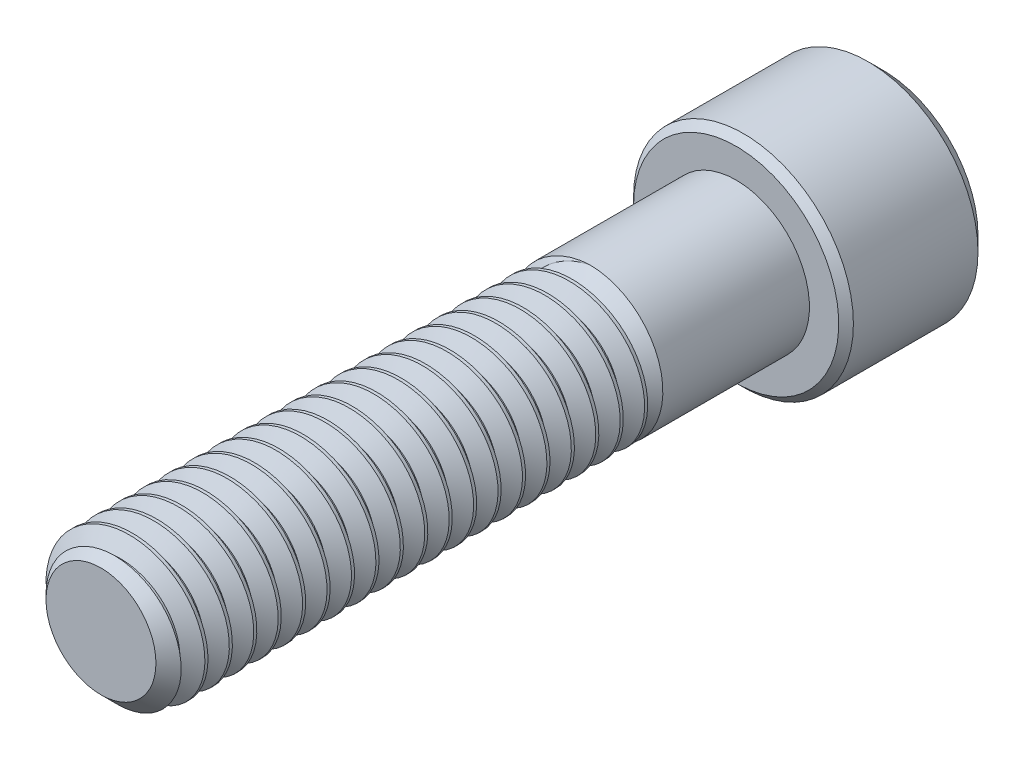
SolidWorks part; units mm, degrees
ref_plane "Front Plane" through (0, 0, 0) normal (0, 0, 1) x (1, 0, 0)
ref_plane "Top Plane" through (0, 0, 0) normal (0, 1, 0) x (1, 0, 0)
ref_plane "Right Plane" through (0, 0, 0) normal (1, 0, 0) x (0, 0, -1)
sketch "Sketch1" plane through (0, 0, 0) normal (0, 0, 1) x (1, 0, 0)
  line L0 (0, 4.7625) -> (0, -4.7625) construction
  circle A0 centre (0, 0) radius 4.7625
  dimension "OD" = 9.525
extrude "Extrude1" add sketch "Sketch1" against normal blind 41.275
sketch "Sketch2" plane through (0, 0, 0) normal (0, 0, 1) x (1, 0, 0)
  circle A0 centre (0, 0) radius 4.7625 construction
  circle A1 centre (0, 0) radius 4.7625
curve "Helix/Spiral1" pitch 1.5875 height 34.925 turns 22 parameters "pitch"=1.5875
chamfer "Chamfer3" distance 1.1906 angle 45 1 edges at (4.7625, 0, 0)
sketch "Sketch3" plane through (0, 0, 0) normal (1, 0, 0) x (0, 0, -1)
  line L0 (-1.3891, 4.7625) -> (-0.7938, 3.7314)
  line L1 (-0.7938, 3.7314) -> (-0.5953, 3.7314)
  line L2 (-0.5953, 3.7314) -> (0, 4.7625)
  line L3 (-1.3891, 4.7625) -> (0, 4.7625)
  line L4 (-0.6945, 4.7625) -> (-0.6945, 3.7314) construction
  line L5 (-1.0914, 4.2469) -> (-0.2977, 4.2469) construction
  line L6 (0, 4.7625) -> (0, -4.7625) construction
  dimension "D1" = 0.1984
  dimension "D2" = 0.7937
  dimension "D3" = 60
sweep "Cut-Sweep1" cut profiles "Sketch3" path "Helix/Spiral1"
sketch "Sketch5" plane through (0, 0, 0) normal (1, 0, 0) x (0, 0, -1)
  line L1 (41.275, 4.7625) -> (31.75, 4.7625)
  line L2 (41.275, 4.7625) -> (41.275, 0)
  line L3 (41.275, 0) -> (31.75, 0)
  line L4 (31.75, 4.7625) -> (31.75, 0) construction
  line L6 (0, 0) -> (9.9695, 0) construction
  line L8 (31.75, 4.7625) -> (26.9875, 0)
  line L9 (26.9875, 0) -> (31.75, 0)
  line L10 (41.275, -4.7625) -> (41.275, 4.7625) construction
  dimension "Thread min" = 31.75
  dimension "D1" = 45
revolve "partially thread" add sketch "Sketch5" angle 360 about L6
sketch "Sketch6" plane through (0, 0, -41.275) normal (0, 0, -1) x (-1, 0, 0)
  circle A0 centre (0, 0) radius 7.1438
  dimension "head dia" = 14.2875
extrude "Extrude2" add sketch "Sketch6" along normal blind 9.525
sketch "Sketch7" plane through (0, 0, -50.8) normal (0, 0, -1) x (-1, 0, 0)
  line L1 (0, 4.5827) -> (-3.9688, 2.2914)
  line L2 (-3.9688, 2.2914) -> (-3.9688, -2.2914)
  line L3 (-3.9688, -2.2914) -> (0, -4.5827)
  line L4 (0, -4.5827) -> (3.9688, -2.2914)
  line L5 (3.9688, -2.2914) -> (3.9688, 2.2914)
  line L6 (3.9688, 2.2914) -> (0, 4.5827)
  circle A0 centre (0, 0) radius 3.9688 construction
  dimension "hex dia" = 7.9375
extrude "Cut-Extrude1" cut sketch "Sketch7" against normal blind 5.9531
sketch "Sketch8" plane through (0, 0, -50.8) normal (0, 0, -1) x (-1, 0, 0)
  circle A0 centre (0, 0) radius 4.5827
extrude "Cut-Extrude2" cut sketch "Sketch8" against normal blind 0.9525 draft 45
chamfer "Chamfer1" distance 0.9525 angle 45 1 edges at (-7.1438, 0, -50.8)
chamfer "Chamfer2" distance 0.4763 angle 45 1 edges at (-7.1438, 0, -41.275)
sketch "Sketch9" plane through (0, 0, 0) normal (1, 0, 0) x (0, 0, -1)
  line L0 (0, 4.7625) -> (0, -4.7625) construction
  line L1 (8.7312, 4.7625) -> (8.7312, -4.7625) construction
  line L2 (41.275, 7.1437) -> (41.275, -7.1438) construction
  line L3 (50.8, 7.1437) -> (50.8, -7.1437) construction
  line L4 (50.8, 0) -> (0, 0) construction
  line L5 (61.6852, 4.7625) -> (61.6852, -4.7625) construction
  dimension "D1" = 8.7312
  dimension "D2" = 9.525
  dimension "D3" = 14.2875
  dimension "D4" = 41.275
  dimension "Thread Length" = 61.6852
equation "\"D3@Helix/Spiral1\" = \"Thread min@Sketch5\"+(\"pitch@Helix/Spiral1\"*2)"
equation "\"D1@Sketch3\" = \"pitch@Helix/Spiral1\"*.125"
equation "\"D2@Sketch3\" = \"pitch@Helix/Spiral1\"*.5"
equation "\"D1@Cut-Extrude1\" = \"hex dia@Sketch7\"*.75"
equation "\"D1@Chamfer1\" = \"head depth@Extrude2\"/10"
equation "\"D1@Sketch9\" = \"pitch@Helix/Spiral1\"*5.5"
equation "\"D1@Chamfer2\" = \"D1@Chamfer1\"/2"
equation "\"D1@Cut-Extrude2\" = \"D1@Chamfer2\"*2"
equation "\"D1@Chamfer3\" = \"pitch@Helix/Spiral1\"*.750"
equation "\"D2@Sketch9\" = \"head depth@Extrude2\""
equation "\"D3@Sketch9\" = \"head dia@Sketch6\""
equation "\"D4@Sketch9\" = \"screw length@Extrude1\""
